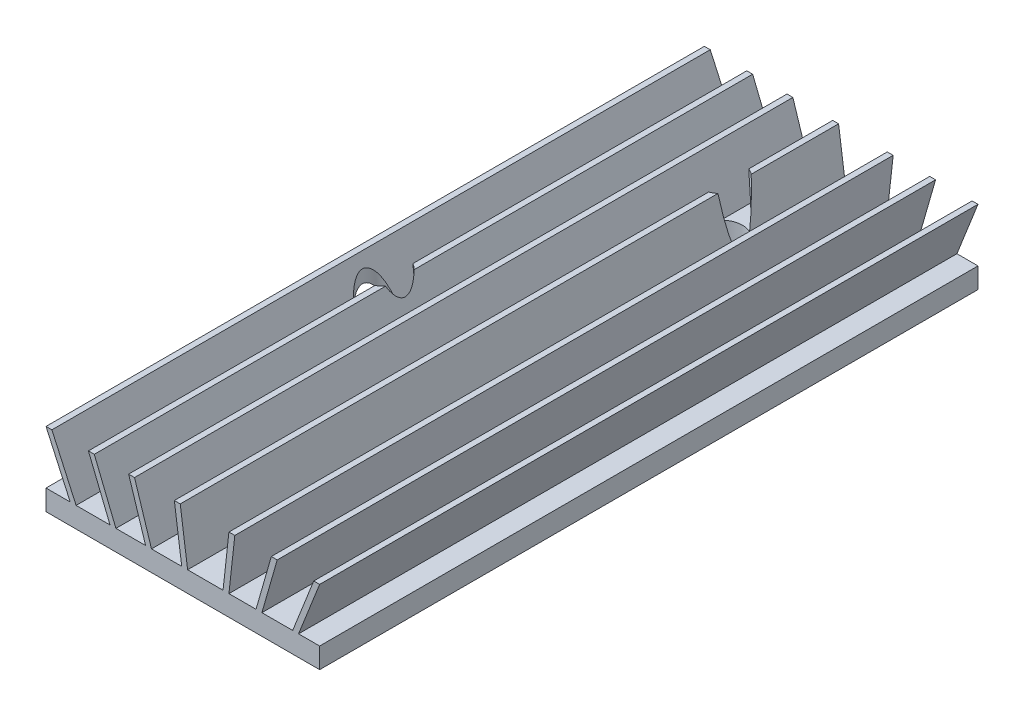
SolidWorks part; units mm, degrees
ref_plane "Front Plane" through (0, 0, 0) normal (0, 0, 1) x (1, 0, 0)
ref_plane "Top Plane" through (0, 0, 0) normal (0, 1, 0) x (1, 0, 0)
ref_plane "Right Plane" through (0, 0, 0) normal (1, 0, 0) x (0, 0, -1)
sketch "Sketch1" plane through (0, 0, 0) normal (0, 0, 1) x (1, 0, 0)
  line L1 (0, 0) -> (25.4, 0)
  line L2 (0, 0) -> (0, 1.905)
  line L3 (0, 1.905) -> (25.4, 1.905)
  line L4 (25.4, 0) -> (25.4, 1.905)
  dimension "D1" = 1.905
  dimension "D2" = 25.4
extrude "Base" add sketch "Sketch1" along normal blind 61.1124
sketch "Sketch2" plane through (0, 0, 0) normal (0, 0, -1) x (-1, 0, 0)
  line L0 (-23.4443, 1.905) -> (-25.4, 6.858)
  line L1 (-25.4, 6.858) -> (-24.8538, 6.858)
  line L2 (-24.8538, 6.858) -> (-22.8981, 1.905)
  line L3 (-25.4, 1.905) -> (0, 1.905) construction
  line L4 (-23.4443, 1.905) -> (-22.8981, 1.905)
  line L5 (0, 0) -> (-25.4, 0) construction
  line L6 (-20.0405, 1.905) -> (-19.4944, 1.905)
  line L7 (-19.4944, 1.905) -> (-20.9168, 6.858)
  line L8 (-20.9168, 6.858) -> (-21.463, 6.858)
  line L9 (-21.463, 6.858) -> (-20.0405, 1.905)
  line L10 (-16.9798, 1.905) -> (-16.4337, 1.905)
  line L11 (0, 1.905) -> (0, 0) construction
  line L12 (-2.794, 1.905) -> (-2.2478, 1.905)
  line L13 (-2.2478, 1.905) -> (0, 6.858)
  line L14 (0, 6.858) -> (-0.5462, 6.858)
  line L15 (-0.5462, 6.858) -> (-2.794, 1.905)
  line L16 (-16.4337, 1.905) -> (-16.9798, 6.858)
  line L17 (-16.9798, 6.858) -> (-17.526, 6.858)
  line L18 (-17.526, 6.858) -> (-16.9798, 1.905)
  line L19 (-12.4588, 6.858) -> (-11.9126, 6.858)
  line L20 (-11.9126, 6.858) -> (-12.5983, 1.905)
  line L21 (-12.5983, 1.905) -> (-13.1444, 1.905)
  line L22 (-13.1444, 1.905) -> (-12.4588, 6.858)
  line L23 (-8.217, 6.858) -> (-7.6708, 6.858)
  line L24 (-7.6708, 6.858) -> (-9.2455, 1.905)
  line L25 (-9.2455, 1.905) -> (-9.7916, 1.905)
  line L26 (-9.7916, 1.905) -> (-8.217, 6.858)
  line L27 (-4.4832, 6.858) -> (-3.937, 6.858)
  line L28 (-3.937, 6.858) -> (-5.9435, 1.905)
  line L29 (-5.9435, 1.905) -> (-6.4896, 1.905)
  line L30 (-6.4896, 1.905) -> (-4.4832, 6.858)
  dimension "D1" = 0.508
  dimension "D2" = 6.858
  dimension "D3" = 2.5019
  dimension "D4" = 21.463
  dimension "D5" = 2.794
  dimension "D6" = 17.7927
  dimension "D7" = 14.732
  dimension "D8" = 17.526
  dimension "D9" = 10.8966
  dimension "D10" = 13.4874
  dimension "D11" = 7.5438
  dimension "D12" = 17.7292
  dimension "D13" = 4.2418
  dimension "D14" = 21.463
extrude "Fins" add sketch "Sketch2" against normal up to surface (61.1124 mm away) up to face at (12.7, 0.9525, 61.1124)
sketch "Sketch3" plane through (0, 1.905, 0) normal (0, 1, 0) x (1, 0, 0)
  line L4 (2.794, -61.1124) -> (5.9435, -61.1124)
  line L5 (5.9435, -61.1124) -> (5.9435, 0)
  line L6 (5.9435, 0) -> (2.794, 0)
  line L7 (2.794, 0) -> (2.794, -61.1124)
  line L8 (2.794, -61.1124) -> (5.9435, -61.1124)
  line L9 (5.9435, -61.1124) -> (5.9435, 0)
  line L10 (5.9435, 0) -> (2.794, 0)
  circle A0 centre (11.2, -9.655) radius 1.9939 construction
  circle A1 centre (11.2, -9.655) radius 1.9939
  circle A2 centre (3, -32.755) radius 1.9939 construction
  circle A3 centre (3, -32.755) radius 1.9939
  dimension "D1" = 0
extrude "Cut-Extrude1" cut sketch "Sketch3" against normal through all and the other way through all contours A1 | A3
